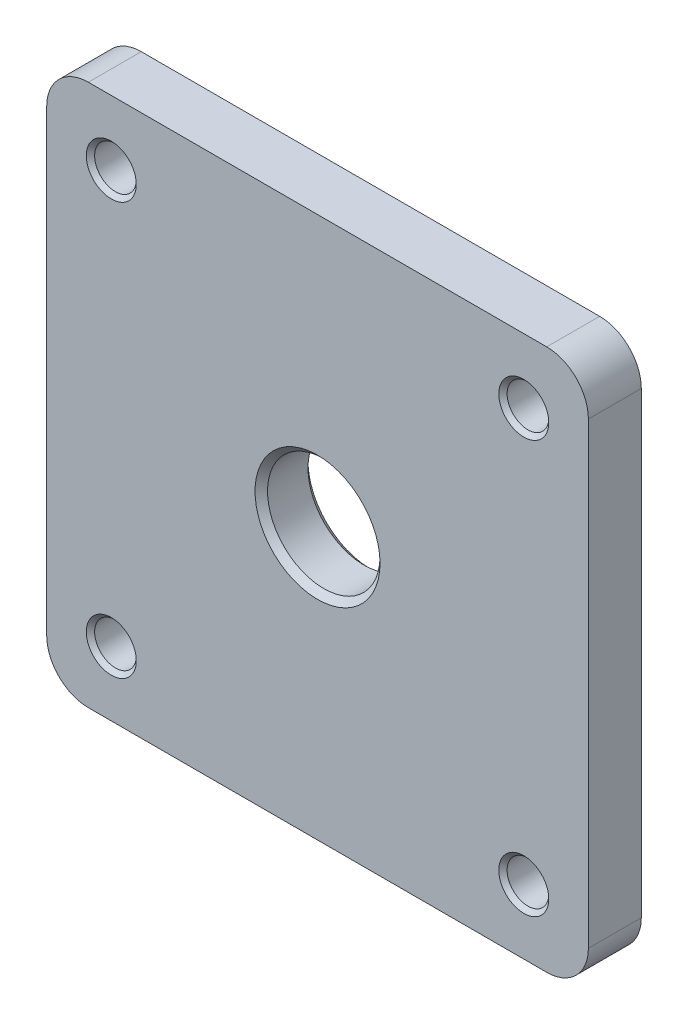
SolidWorks part; units mm, degrees
material "6061 Alloy"
ref_plane "Front Plane" through (0, 0, 0) normal (0, 0, 1) x (1, 0, 0)
ref_plane "Top Plane" through (0, 0, 0) normal (0, 1, 0) x (1, 0, 0)
ref_plane "Right Plane" through (0, 0, 0) normal (1, 0, 0) x (0, 0, -1)
sketch "Sketch1" plane through (0, 0, 0) normal (0, 0, 1) x (1, 0, 0)
  line L1 (-32.5, -32.5) -> (32.5, -32.5)
  line L2 (-32.5, -32.5) -> (-32.5, 32.5)
  line L3 (-32.5, 32.5) -> (32.5, 32.5)
  line L4 (32.5, -32.5) -> (32.5, 32.5)
  line L5 (-32.5, -32.5) -> (32.5, 32.5) construction
  line L6 (-32.5, 32.5) -> (32.5, -32.5) construction
  point P0 (0, 0)
  dimension "D1" = 65
extrude "1/4 in Sheet Metal" add sketch "Sketch1" along normal mid plane 6.35
hole_wizard "M12 Clearance Hole1" positions "Sketch3" profile "Sketch4" hole size "M12" standard "ANSI Metric" end condition up to next
sketch "Sketch3" plane through (0, 0, 3.175) normal (0, 0, 1) x (1, 0, 0)
  point P0 (0, 0)
sketch "Sketch4" plane through (0, 0, 3.175) normal (1, 0, 0) x (0, -1, 0)
  line L0 (0, 0) -> (0, 6.35)
  line L1 (0, 6.35) -> (7.5, 6.35)
  line L2 (6.75, 5.6) -> (6.75, 0.75)
  line L3 (6.75, 0.75) -> (7.5, 0)
  line L5 (7.5, 0) -> (0, 0)
  line L6 (-6.75, 0.75) -> (-7.5, 0) construction
  line L7 (7.5, 6.35) -> (6.75, 5.6)
  line L8 (-7.5, 6.35) -> (-6.75, 5.6) construction
  line L11 (0, -6.35) -> (0, 107.95) construction
  dimension "Thru Hole Dia." = 13.5
  dimension "Thru Hole Depth" = 6.35
  dimension "Near C'Sink Dia." = 15
  dimension "Near C'Sink Angle" = 90
  dimension "Far C'Sink Dia." = 15
  dimension "Far C'Sink Angle" = 90
sketch "Sketch2" plane through (0, 0, 0) normal (0, 0, 1) x (1, 0, 0)
  line L0 (-24.7487, -24.7487) -> (24.7487, 24.7487) construction
  line L1 (-24.7487, 24.7487) -> (24.7487, -24.7487) construction
  line L2 (0, 0) -> (32.5, 0) construction
  line L3 (32.5, -32.5) -> (32.5, 32.5) construction
  circle A0 centre (24.7487, 24.7487) radius 2.5
  circle A1 centre (-24.7487, 24.7487) radius 2.5
  circle A2 centre (-24.7487, -24.7487) radius 2.5
  circle A3 centre (24.7487, -24.7487) radius 2.5
  circle A4 centre (0, 0) radius 35 construction
  dimension "D1" = 5
  dimension "D2" = 70
  dimension "D3" = 45
extrude "M5 Clearance Holes" cut sketch "Sketch2" against normal through all both and the other way through all
fillet "Fillet1" radius 5 4 edges at (-32.5, -32.5, 0) (-32.5, 32.5, 0) (32.5, -32.5, 0) (32.5, 32.5, 0)
chamfer "Chamfer1" distance 0.5 angle 45 8 edges at (27.2487, -24.7487, 3.175) (27.2487, -24.7487, -3.175) (-22.2487, -24.7487, 3.175) (-22.2487, -24.7487, -3.175) (-22.2487, 24.7487, 3.175) (-22.2487, 24.7487, -3.175) (27.2487, 24.7487, 3.175) (27.2487, 24.7487, -3.175)
